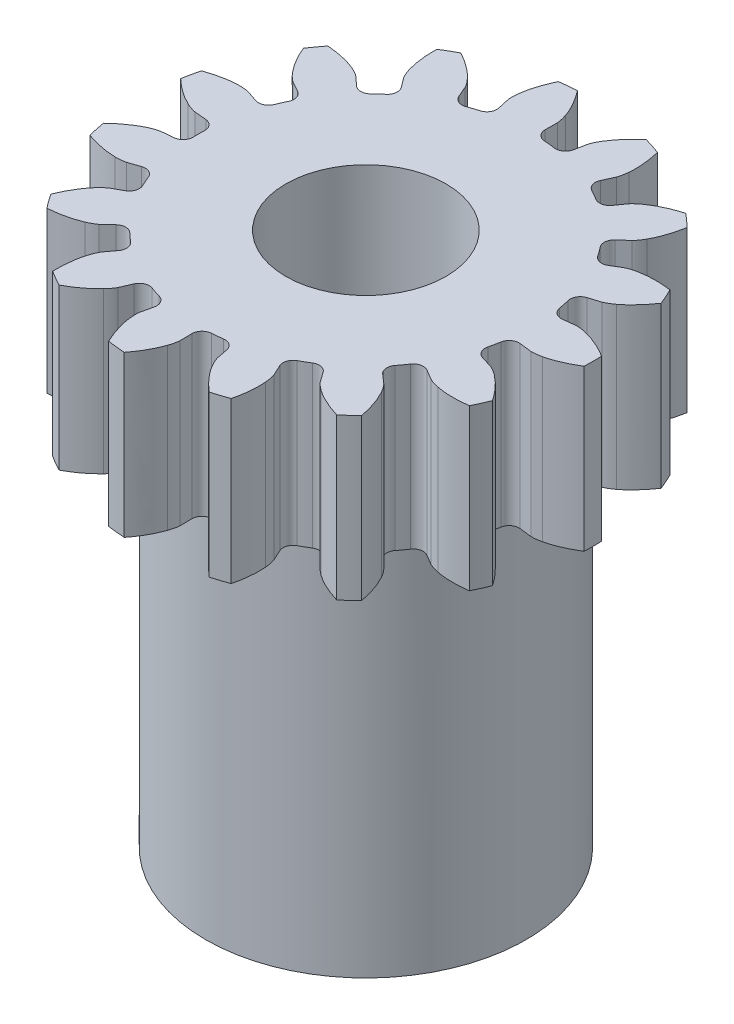
SolidWorks part; units mm, degrees
ref_plane "Front Plane" through (0, 0, 0) normal (0, 0, 1) x (1, 0, 0)
ref_plane "Top Plane" through (0, 0, 0) normal (0, 1, 0) x (1, 0, 0)
ref_plane "Right Plane" through (0, 0, 0) normal (1, 0, 0) x (0, 0, -1)
sketch "Sketch1" plane through (0, 0, 3) normal (0, -1, 0) x (1, 0, 0)
  line L0 (3.2832, -3.3946) -> (3.507, -3.4211)
  line L1 (3.507, -2.5789) -> (3.2832, -2.6054)
  line L2 (3.1599, -2.0251) -> (3.3751, -1.9583)
  line L3 (3.0325, -1.1889) -> (2.8389, -1.3041)
  line L4 (2.4902, -0.8241) -> (2.6596, -0.6756)
  line L5 (2.0336, -0.112) -> (1.9036, -0.296)
  line L6 (1.3899, 0.0006) -> (1.4842, 0.2052)
  line L7 (0.6832, 0.4655) -> (0.6393, 0.2445)
  line L8 (0.0493, 0.3065) -> (0.0523, 0.5318)
  line L9 (-0.7854, 0.4437) -> (-0.7357, 0.224)
  line L10 (-1.2998, 0.0407) -> (-1.3888, 0.2477)
  line L11 (-2.1182, -0.1735) -> (-1.9834, -0.354)
  line L12 (-2.4242, -0.7509) -> (-2.5897, -0.598)
  line L13 (-3.0847, -1.2794) -> (-2.8882, -1.3894)
  line L14 (-3.1294, -1.9314) -> (-3.3428, -1.8589)
  line L15 (-3.5179, -2.6828) -> (-3.2935, -2.7034)
  line L16 (-3.2935, -3.2966) -> (-3.5179, -3.3172)
  line L17 (-3.3428, -4.1411) -> (-3.1294, -4.0686)
  line L18 (-2.8882, -4.6106) -> (-3.0847, -4.7206)
  line L19 (-2.5897, -5.402) -> (-2.4242, -5.2491)
  line L20 (-1.9834, -5.646) -> (-2.1182, -5.8265)
  line L21 (-1.3888, -6.2477) -> (-1.2998, -6.0407)
  line L22 (-0.7357, -6.224) -> (-0.7854, -6.4437)
  line L23 (0.0523, -6.5318) -> (0.0493, -6.3065)
  line L24 (0.6393, -6.2445) -> (0.6832, -6.4655)
  line L25 (1.4842, -6.2052) -> (1.3899, -6.0006)
  line L26 (1.9036, -5.704) -> (2.0336, -5.888)
  line L27 (2.6596, -5.3244) -> (2.4902, -5.1759)
  line L28 (2.8389, -4.6959) -> (3.0325, -4.8111)
  line L29 (3.3751, -4.0417) -> (3.1599, -3.9749)
  arc A0 (3.0335, -3.7508) -> (3.0766, -3.548) centre (0, -3) ccw
  arc A1 (3.0766, -3.548) -> (3.2832, -3.3946) centre (3.2612, -3.5808) cw
  arc A2 (4.2475, -3.1638) -> (4.2475, -2.8362) centre (0.0006, -3) ccw
  arc A3 (3.2832, -2.6054) -> (3.0766, -2.452) centre (3.2612, -2.4192) cw
  arc A4 (3.0766, -2.452) -> (3.0335, -2.2492) centre (0, -3) ccw
  arc A5 (3.0335, -2.2492) -> (3.1599, -2.0251) centre (3.2155, -2.2042) cw
  arc A6 (3.9469, -1.4221) -> (3.8136, -1.1228) centre (0.0006, -2.9998) ccw
  arc A7 (2.8389, -1.3041) -> (2.5877, -1.2481) centre (2.743, -1.1429) cw
  arc A8 (2.5877, -1.2481) -> (2.4658, -1.0803) centre (0, -3) ccw
  arc A9 (2.4658, -1.0803) -> (2.4902, -0.8241) centre (2.6138, -0.9651) cw
  arc A10 (2.9638, 0.0469) -> (2.7204, 0.2661) centre (0.0004, -2.9995) ccw
  arc A11 (1.9036, -0.296) -> (1.6514, -0.347) centre (1.7505, -0.1878) cw
  arc A12 (1.6514, -0.347) -> (1.4719, -0.2433) centre (0, -3) ccw
  arc A13 (1.4719, -0.2433) -> (1.3899, 0.0006) centre (1.5602, -0.0779) cw
  arc A14 (1.4683, 0.9889) -> (1.1567, 1.0902) centre (0.0002, -2.9994) ccw
  arc A15 (0.6393, 0.2445) -> (0.4296, 0.0953) centre (0.4554, 0.2811) cw
  arc A16 (0.4296, 0.0953) -> (0.2234, 0.117) centre (0, -3) ccw
  arc A17 (0.2234, 0.117) -> (0.0493, 0.3065) centre (0.2368, 0.304) cw
  arc A18 (-0.2811, 1.2413) -> (-0.6069, 1.2071) centre (-0.0001, -2.9994) ccw
  arc A19 (-0.7357, 0.224) -> (-0.8665, 0.0025) centre (-0.9185, 0.1826) cw
  arc A20 (-0.8665, 0.0025) -> (-1.0637, -0.0616) centre (0, -3) ccw
  arc A21 (-1.0637, -0.0616) -> (-1.2998, 0.0407) centre (-1.1276, 0.1147) cw
  arc A22 (-1.9819, 0.7603) -> (-2.2656, 0.5965) centre (-0.0003, -2.9995) ccw
  arc A23 (-1.9834, -0.354) -> (-2.0128, -0.6096) centre (-2.1336, -0.4662) cw
  arc A24 (-2.0128, -0.6096) -> (-2.1669, -0.7483) centre (0, -3) ccw
  arc A25 (-2.1669, -0.7483) -> (-2.4242, -0.7509) centre (-2.2969, -0.6132) cw
  arc A26 (-3.34, -0.3709) -> (-3.5325, -0.6359) centre (-0.0005, -2.9996) ccw
  arc A27 (-2.8882, -1.3894) -> (-2.8111, -1.6349) centre (-2.9798, -1.553) cw
  arc A28 (-2.8111, -1.6349) -> (-2.8954, -1.8244) centre (0, -3) ccw
  arc A29 (-2.8954, -1.8244) -> (-3.1294, -1.9314) centre (-3.0692, -1.7538) cw
  arc A30 (-4.1206, -1.9567) -> (-4.1887, -2.2771) centre (-0.0006, -2.9999) ccw
  arc A31 (-3.2935, -2.7034) -> (-3.1233, -2.8963) centre (-3.3107, -2.8901) cw
  arc A32 (-3.1233, -2.8963) -> (-3.1233, -3.1037) centre (0, -3) ccw
  arc A33 (-3.1233, -3.1037) -> (-3.2935, -3.2966) centre (-3.3107, -3.1099) cw
  arc A34 (-4.1887, -3.7229) -> (-4.1206, -4.0433) centre (-0.0006, -3.0001) ccw
  arc A35 (-3.1294, -4.0686) -> (-2.8954, -4.1756) centre (-3.0692, -4.2462) cw
  arc A36 (-2.8954, -4.1756) -> (-2.8111, -4.3651) centre (0, -3) ccw
  arc A37 (-2.8111, -4.3651) -> (-2.8882, -4.6106) centre (-2.9798, -4.447) cw
  arc A38 (-3.5325, -5.3641) -> (-3.34, -5.6291) centre (-0.0005, -3.0004) ccw
  arc A39 (-2.4242, -5.2491) -> (-2.1669, -5.2517) centre (-2.2969, -5.3868) cw
  arc A40 (-2.1669, -5.2517) -> (-2.0128, -5.3904) centre (0, -3) ccw
  arc A41 (-2.0128, -5.3904) -> (-1.9834, -5.646) centre (-2.1336, -5.5338) cw
  arc A42 (-2.2656, -6.5965) -> (-1.9819, -6.7603) centre (-0.0003, -3.0005) ccw
  arc A43 (-1.2998, -6.0407) -> (-1.0637, -5.9384) centre (-1.1276, -6.1147) cw
  arc A44 (-1.0637, -5.9384) -> (-0.8665, -6.0025) centre (0, -3) ccw
  arc A45 (-0.8665, -6.0025) -> (-0.7357, -6.224) centre (-0.9185, -6.1826) cw
  arc A46 (-0.6069, -7.2071) -> (-0.2811, -7.2413) centre (-0.0001, -3.0006) ccw
  arc A47 (0.0493, -6.3065) -> (0.2234, -6.117) centre (0.2368, -6.304) cw
  arc A48 (0.2234, -6.117) -> (0.4296, -6.0953) centre (0, -3) ccw
  arc A49 (0.4296, -6.0953) -> (0.6393, -6.2445) centre (0.4554, -6.2811) cw
  arc A50 (1.1567, -7.0902) -> (1.4683, -6.9889) centre (0.0002, -3.0006) ccw
  arc A51 (1.3899, -6.0006) -> (1.4719, -5.7567) centre (1.5602, -5.9221) cw
  arc A52 (1.4719, -5.7567) -> (1.6514, -5.653) centre (0, -3) ccw
  arc A53 (1.6514, -5.653) -> (1.9036, -5.704) centre (1.7505, -5.8122) cw
  arc A54 (2.7204, -6.2661) -> (2.9638, -6.0469) centre (0.0004, -3.0005) ccw
  arc A55 (2.4902, -5.1759) -> (2.4658, -4.9197) centre (2.6138, -5.0349) cw
  arc A56 (2.4658, -4.9197) -> (2.5877, -4.7519) centre (0, -3) ccw
  arc A57 (2.5877, -4.7519) -> (2.8389, -4.6959) centre (2.743, -4.8571) cw
  arc A58 (3.8136, -4.8772) -> (3.9469, -4.5779) centre (0.0006, -3.0002) ccw
  arc A59 (3.1599, -3.9749) -> (3.0335, -3.7508) centre (3.2155, -3.7958) cw
  spline S0 degree 3 poles (3.507, -3.4211) (3.521, -3.4219) (3.535, -3.4216) (3.549, -3.4209) (3.5749, -3.4196) (3.6007, -3.4167) (3.6264, -3.4128) (3.6522, -3.4089) (3.6779, -3.404) (3.7033, -3.3983) knots 0 0 0 0 0.000042 0.000042 0.000042 0.00012 0.00012 0.00012 0.000198 0.000198 0.000198 0.000198
  spline S1 degree 3 poles (3.7033, -3.3983) (3.7685, -3.3834) (3.8326, -3.3634) (3.895, -3.3398) (3.9562, -3.3166) (4.0161, -3.29) (4.0746, -3.2606) (4.1336, -3.2309) (4.1912, -3.1985) (4.2475, -3.1638) knots 0 0 0 0 0.0002 0.0002 0.0002 0.000397 0.000397 0.000397 0.000594 0.000594 0.000594 0.000594
  spline S2 degree 3 poles (4.2475, -2.8362) (4.1907, -2.8012) (4.1324, -2.7684) (4.0728, -2.7385) (4.0144, -2.7092) (3.9545, -2.6826) (3.8934, -2.6596) (3.8314, -2.6363) (3.7679, -2.6164) (3.7033, -2.6017) knots 0 0 0 0 0.0002 0.0002 0.0002 0.000396 0.000396 0.000396 0.000595 0.000595 0.000595 0.000595
  spline S3 degree 3 poles (3.7033, -2.6017) (3.676, -2.5956) (3.6484, -2.5904) (3.6207, -2.5864) (3.6019, -2.5837) (3.5831, -2.5815) (3.5642, -2.5801) (3.5452, -2.5787) (3.526, -2.5779) (3.507, -2.5789) knots 0 0 0 0 0.000084 0.000084 0.000084 0.000141 0.000141 0.000141 0.000198 0.000198 0.000198 0.000198
  spline S4 degree 3 poles (3.3751, -1.9583) (3.3882, -1.9533) (3.4009, -1.9473) (3.4134, -1.941) (3.4365, -1.9292) (3.4589, -1.9161) (3.4807, -1.9021) (3.5027, -1.8881) (3.5242, -1.8731) (3.5452, -1.8575) knots 0 0 0 0 0.000042 0.000042 0.000042 0.00012 0.00012 0.00012 0.000198 0.000198 0.000198 0.000198
  spline S5 degree 3 poles (3.5452, -1.8575) (3.5986, -1.8175) (3.649, -1.7731) (3.6965, -1.7261) (3.743, -1.6801) (3.7869, -1.6314) (3.8283, -1.5808) (3.8702, -1.5297) (3.9096, -1.4766) (3.9469, -1.4221) knots 0 0 0 0 0.0002 0.0002 0.0002 0.000397 0.000397 0.000397 0.000594 0.000594 0.000594 0.000594
  spline S6 degree 3 poles (3.8136, -1.1228) (3.7475, -1.1139) (3.681, -1.1076) (3.6144, -1.1046) (3.5491, -1.1016) (3.4835, -1.1016) (3.4183, -1.1055) (3.3522, -1.1093) (3.2861, -1.1171) (3.2212, -1.1299) knots 0 0 0 0 0.0002 0.0002 0.0002 0.000396 0.000396 0.000396 0.000595 0.000595 0.000595 0.000595
  spline S7 degree 3 poles (3.2212, -1.1299) (3.1937, -1.1354) (3.1664, -1.1419) (3.1394, -1.1495) (3.1212, -1.1546) (3.1031, -1.1603) (3.0853, -1.1667) (3.0673, -1.1731) (3.0495, -1.1802) (3.0325, -1.1889) knots 0 0 0 0 0.000084 0.000084 0.000084 0.000141 0.000141 0.000141 0.000198 0.000198 0.000198 0.000198
  spline S8 degree 3 poles (2.6596, -0.6756) (2.6695, -0.6657) (2.6787, -0.655) (2.6875, -0.6442) (2.7039, -0.6241) (2.719, -0.6029) (2.7333, -0.5813) (2.7476, -0.5595) (2.7612, -0.5371) (2.774, -0.5144) knots 0 0 0 0 0.000042 0.000042 0.000042 0.00012 0.00012 0.00012 0.000198 0.000198 0.000198 0.000198
  spline S9 degree 3 poles (2.774, -0.5144) (2.8066, -0.456) (2.8345, -0.395) (2.8588, -0.3328) (2.8825, -0.2718) (2.9028, -0.2095) (2.9201, -0.1464) (2.9375, -0.0827) (2.952, -0.0181) (2.9638, 0.0469) knots 0 0 0 0 0.0002 0.0002 0.0002 0.000397 0.000397 0.000397 0.000594 0.000594 0.000594 0.000594
  spline S10 degree 3 poles (2.7204, 0.2661) (2.6564, 0.2473) (2.593, 0.226) (2.5309, 0.2017) (2.4701, 0.1778) (2.4102, 0.1511) (2.3522, 0.1211) (2.2934, 0.0907) (2.2362, 0.0568) (2.1821, 0.0186) knots 0 0 0 0 0.0002 0.0002 0.0002 0.000396 0.000396 0.000396 0.000595 0.000595 0.000595 0.000595
  spline S11 degree 3 poles (2.1821, 0.0186) (2.1592, 0.0024) (2.1369, -0.0146) (2.1153, -0.0325) (2.1008, -0.0447) (2.0865, -0.0572) (2.0728, -0.0703) (2.0591, -0.0835) (2.0457, -0.0972) (2.0336, -0.112) knots 0 0 0 0 0.000084 0.000084 0.000084 0.000141 0.000141 0.000141 0.000198 0.000198 0.000198 0.000198
  spline S12 degree 3 poles (1.4842, 0.2052) (1.4893, 0.2183) (1.4933, 0.2317) (1.497, 0.2453) (1.5037, 0.2703) (1.509, 0.2957) (1.5132, 0.3213) (1.5175, 0.3471) (1.5207, 0.373) (1.5232, 0.399) knots 0 0 0 0 0.000042 0.000042 0.000042 0.00012 0.00012 0.00012 0.000198 0.000198 0.000198 0.000198
  spline S13 degree 3 poles (1.5232, 0.399) (1.5292, 0.4656) (1.5299, 0.5327) (1.5268, 0.5994) (1.5237, 0.6647) (1.5168, 0.73) (1.507, 0.7946) (1.497, 0.8599) (1.4839, 0.9248) (1.4683, 0.9889) knots 0 0 0 0 0.0002 0.0002 0.0002 0.000397 0.000397 0.000397 0.000594 0.000594 0.000594 0.000594
  spline S14 degree 3 poles (1.1567, 1.0902) (1.1059, 1.047) (1.0567, 1.0018) (1.0099, 0.9543) (0.964, 0.9078) (0.9202, 0.859) (0.8794, 0.808) (0.838, 0.7563) (0.7996, 0.702) (0.7656, 0.6452) knots 0 0 0 0 0.0002 0.0002 0.0002 0.000396 0.000396 0.000396 0.000595 0.000595 0.000595 0.000595
  spline S15 degree 3 poles (0.7656, 0.6452) (0.7514, 0.621) (0.7379, 0.5964) (0.7255, 0.5713) (0.7171, 0.5543) (0.7092, 0.537) (0.702, 0.5195) (0.6948, 0.5018) (0.6881, 0.4839) (0.6832, 0.4655) knots 0 0 0 0 0.000084 0.000084 0.000084 0.000141 0.000141 0.000141 0.000198 0.000198 0.000198 0.000198
  spline S16 degree 3 poles (0.0523, 0.5318) (0.0515, 0.5458) (0.0497, 0.5597) (0.0476, 0.5736) (0.0436, 0.5992) (0.038, 0.6246) (0.0315, 0.6496) (0.0249, 0.6749) (0.0173, 0.6999) (0.009, 0.7247) knots 0 0 0 0 0.000042 0.000042 0.000042 0.00012 0.00012 0.00012 0.000198 0.000198 0.000198 0.000198
  spline S17 degree 3 poles (0.009, 0.7247) (-0.0126, 0.7879) (-0.0392, 0.8495) (-0.0692, 0.9092) (-0.0986, 0.9677) (-0.1314, 1.0245) (-0.1667, 1.0795) (-0.2024, 1.1351) (-0.2407, 1.189) (-0.2811, 1.2413) knots 0 0 0 0 0.0002 0.0002 0.0002 0.000397 0.000397 0.000397 0.000594 0.000594 0.000594 0.000594
  spline S18 degree 3 poles (-0.6069, 1.2071) (-0.6358, 1.1469) (-0.6623, 1.0856) (-0.6858, 1.0232) (-0.7088, 0.962) (-0.729, 0.8997) (-0.7455, 0.8365) (-0.7622, 0.7724) (-0.7753, 0.7072) (-0.7832, 0.6414) knots 0 0 0 0 0.0002 0.0002 0.0002 0.000396 0.000396 0.000396 0.000595 0.000595 0.000595 0.000595
  spline S19 degree 3 poles (-0.7832, 0.6414) (-0.7864, 0.6136) (-0.7887, 0.5856) (-0.7898, 0.5576) (-0.7906, 0.5387) (-0.7908, 0.5197) (-0.7902, 0.5008) (-0.7896, 0.4817) (-0.7884, 0.4626) (-0.7854, 0.4437) knots 0 0 0 0 0.000084 0.000084 0.000084 0.000141 0.000141 0.000141 0.000198 0.000198 0.000198 0.000198
  spline S20 degree 3 poles (-1.3888, 0.2477) (-1.3951, 0.2602) (-1.4024, 0.2722) (-1.41, 0.284) (-1.4241, 0.3058) (-1.4395, 0.3267) (-1.4557, 0.3469) (-1.472, 0.3673) (-1.4891, 0.3871) (-1.5068, 0.4063) knots 0 0 0 0 0.000042 0.000042 0.000042 0.00012 0.00012 0.00012 0.000198 0.000198 0.000198 0.000198
  spline S21 degree 3 poles (-1.5068, 0.4063) (-1.5522, 0.4553) (-1.6016, 0.5008) (-1.6533, 0.5431) (-1.7039, 0.5845) (-1.757, 0.6231) (-1.8116, 0.659) (-1.8668, 0.6953) (-1.9237, 0.729) (-1.9819, 0.7603) knots 0 0 0 0 0.0002 0.0002 0.0002 0.000397 0.000397 0.000397 0.000594 0.000594 0.000594 0.000594
  spline S22 degree 3 poles (-2.2656, 0.5965) (-2.2675, 0.5298) (-2.2668, 0.463) (-2.2629, 0.3964) (-2.259, 0.3312) (-2.2521, 0.266) (-2.2415, 0.2016) (-2.2307, 0.1362) (-2.2161, 0.0713) (-2.1966, 0.0081) knots 0 0 0 0 0.0002 0.0002 0.0002 0.000396 0.000396 0.000396 0.000595 0.000595 0.000595 0.000595
  spline S23 degree 3 poles (-2.1966, 0.0081) (-2.1882, -0.0187) (-2.1789, -0.0452) (-2.1686, -0.0712) (-2.1615, -0.0888) (-2.154, -0.1062) (-2.1458, -0.1233) (-2.1375, -0.1405) (-2.1286, -0.1574) (-2.1182, -0.1735) knots 0 0 0 0 0.000084 0.000084 0.000084 0.000141 0.000141 0.000141 0.000198 0.000198 0.000198 0.000198
  spline S24 degree 3 poles (-2.5897, -0.598) (-2.6006, -0.5891) (-2.6121, -0.5811) (-2.6239, -0.5734) (-2.6456, -0.5593) (-2.6682, -0.5465) (-2.6912, -0.5345) (-2.7143, -0.5225) (-2.738, -0.5114) (-2.762, -0.501) knots 0 0 0 0 0.000042 0.000042 0.000042 0.00012 0.00012 0.00012 0.000198 0.000198 0.000198 0.000198
  spline S25 degree 3 poles (-2.762, -0.501) (-2.8234, -0.4747) (-2.887, -0.4533) (-2.9515, -0.4357) (-3.0145, -0.4184) (-3.0787, -0.4048) (-3.1432, -0.3942) (-3.2084, -0.3835) (-3.2741, -0.3759) (-3.34, -0.3709) knots 0 0 0 0 0.0002 0.0002 0.0002 0.000397 0.000397 0.000397 0.000594 0.000594 0.000594 0.000594
  spline S26 degree 3 poles (-3.5325, -0.6359) (-3.5072, -0.6976) (-3.4793, -0.7584) (-3.4487, -0.8176) (-3.4186, -0.8756) (-3.3858, -0.9323) (-3.3499, -0.9869) (-3.3135, -1.0422) (-3.2737, -1.0956) (-3.2302, -1.1454) knots 0 0 0 0 0.0002 0.0002 0.0002 0.000396 0.000396 0.000396 0.000595 0.000595 0.000595 0.000595
  spline S27 degree 3 poles (-3.2302, -1.1454) (-3.2116, -1.1664) (-3.1924, -1.1869) (-3.1723, -1.2064) (-3.1587, -1.2197) (-3.1448, -1.2325) (-3.1303, -1.2447) (-3.1158, -1.2571) (-3.1007, -1.269) (-3.0847, -1.2794) knots 0 0 0 0 0.000084 0.000084 0.000084 0.000141 0.000141 0.000141 0.000198 0.000198 0.000198 0.000198
  spline S28 degree 3 poles (-3.3428, -1.8589) (-3.3563, -1.8553) (-3.3701, -1.8527) (-3.384, -1.8504) (-3.4096, -1.8463) (-3.4354, -1.8438) (-3.4613, -1.8423) (-3.4874, -1.8407) (-3.5135, -1.8402) (-3.5396, -1.8405) knots 0 0 0 0 0.000042 0.000042 0.000042 0.00012 0.00012 0.00012 0.000198 0.000198 0.000198 0.000198
  spline S29 degree 3 poles (-3.5396, -1.8405) (-3.6064, -1.8414) (-3.6733, -1.8477) (-3.7393, -1.8578) (-3.8039, -1.8677) (-3.8681, -1.8814) (-3.9314, -1.8979) (-3.9952, -1.9147) (-4.0584, -1.9345) (-4.1206, -1.9567) knots 0 0 0 0 0.0002 0.0002 0.0002 0.000397 0.000397 0.000397 0.000594 0.000594 0.000594 0.000594
  spline S30 degree 3 poles (-4.1887, -2.2771) (-4.1404, -2.3232) (-4.0903, -2.3673) (-4.0382, -2.409) (-3.9871, -2.4498) (-3.9341, -2.4882) (-3.8791, -2.5235) (-3.8233, -2.5592) (-3.7653, -2.5918) (-3.7052, -2.6196) knots 0 0 0 0 0.0002 0.0002 0.0002 0.000396 0.000396 0.000396 0.000595 0.000595 0.000595 0.000595
  spline S31 degree 3 poles (-3.7052, -2.6196) (-3.6797, -2.6313) (-3.6539, -2.6421) (-3.6276, -2.6518) (-3.6098, -2.6584) (-3.5918, -2.6644) (-3.5736, -2.6697) (-3.5553, -2.675) (-3.5367, -2.6798) (-3.5179, -2.6828) knots 0 0 0 0 0.000084 0.000084 0.000084 0.000141 0.000141 0.000141 0.000198 0.000198 0.000198 0.000198
  spline S32 degree 3 poles (-3.5179, -3.3172) (-3.5317, -3.3194) (-3.5454, -3.3226) (-3.559, -3.3262) (-3.584, -3.3329) (-3.6087, -3.3411) (-3.6329, -3.3502) (-3.6574, -3.3594) (-3.6815, -3.3695) (-3.7052, -3.3804) knots 0 0 0 0 0.000042 0.000042 0.000042 0.00012 0.00012 0.00012 0.000198 0.000198 0.000198 0.000198
  spline S33 degree 3 poles (-3.7052, -3.3804) (-3.7659, -3.4085) (-3.8244, -3.4414) (-3.8806, -3.4775) (-3.9356, -3.5128) (-3.9887, -3.5514) (-4.0397, -3.5922) (-4.0913, -3.6335) (-4.1409, -3.6773) (-4.1887, -3.7229) knots 0 0 0 0 0.0002 0.0002 0.0002 0.000397 0.000397 0.000397 0.000594 0.000594 0.000594 0.000594
  spline S34 degree 3 poles (-4.1206, -4.0433) (-4.0578, -4.0658) (-3.994, -4.0857) (-3.9295, -4.1026) (-3.8662, -4.1191) (-3.8021, -4.1326) (-3.7375, -4.1424) (-3.6721, -4.1524) (-3.6058, -4.1586) (-3.5396, -4.1595) knots 0 0 0 0 0.0002 0.0002 0.0002 0.000396 0.000396 0.000396 0.000595 0.000595 0.000595 0.000595
  spline S35 degree 3 poles (-3.5396, -4.1595) (-3.5116, -4.1598) (-3.4835, -4.1592) (-3.4556, -4.1574) (-3.4367, -4.1561) (-3.4178, -4.1543) (-3.399, -4.1518) (-3.3801, -4.1492) (-3.3612, -4.146) (-3.3428, -4.1411) knots 0 0 0 0 0.000084 0.000084 0.000084 0.000141 0.000141 0.000141 0.000198 0.000198 0.000198 0.000198
  spline S36 degree 3 poles (-3.0847, -4.7206) (-3.0965, -4.7283) (-3.1077, -4.7368) (-3.1186, -4.7456) (-3.1388, -4.7618) (-3.158, -4.7794) (-3.1764, -4.7976) (-3.195, -4.8159) (-3.2129, -4.835) (-3.2302, -4.8546) knots 0 0 0 0 0.000042 0.000042 0.000042 0.00012 0.00012 0.00012 0.000198 0.000198 0.000198 0.000198
  spline S37 degree 3 poles (-3.2302, -4.8546) (-3.2741, -4.9049) (-3.3142, -4.9587) (-3.3509, -5.0146) (-3.3868, -5.0692) (-3.4196, -5.126) (-3.4496, -5.1841) (-3.4799, -5.2428) (-3.5074, -5.303) (-3.5325, -5.3641) knots 0 0 0 0 0.0002 0.0002 0.0002 0.000397 0.000397 0.000397 0.000594 0.000594 0.000594 0.000594
  spline S38 degree 3 poles (-3.34, -5.6291) (-3.2735, -5.6241) (-3.2071, -5.6164) (-3.1413, -5.6055) (-3.0768, -5.5948) (-3.0127, -5.5812) (-2.9497, -5.5639) (-2.8859, -5.5463) (-2.8228, -5.525) (-2.762, -5.499) knots 0 0 0 0 0.0002 0.0002 0.0002 0.000396 0.000396 0.000396 0.000595 0.000595 0.000595 0.000595
  spline S39 degree 3 poles (-2.762, -5.499) (-2.7363, -5.4878) (-2.7109, -5.4759) (-2.6861, -5.4628) (-2.6693, -5.454) (-2.6528, -5.4447) (-2.6367, -5.4347) (-2.6204, -5.4247) (-2.6045, -5.414) (-2.5897, -5.402) knots 0 0 0 0 0.000084 0.000084 0.000084 0.000141 0.000141 0.000141 0.000198 0.000198 0.000198 0.000198
  spline S40 degree 3 poles (-2.1182, -5.8265) (-2.1258, -5.8383) (-2.1326, -5.8506) (-2.139, -5.8631) (-2.1508, -5.8862) (-2.1612, -5.91) (-2.1707, -5.9341) (-2.1802, -5.9584) (-2.1888, -5.9831) (-2.1966, -6.0081) knots 0 0 0 0 0.000042 0.000042 0.000042 0.00012 0.00012 0.00012 0.000198 0.000198 0.000198 0.000198
  spline S41 degree 3 poles (-2.1966, -6.0081) (-2.2163, -6.0719) (-2.231, -6.1374) (-2.2418, -6.2033) (-2.2523, -6.2679) (-2.2592, -6.3331) (-2.263, -6.3984) (-2.2668, -6.4643) (-2.2675, -6.5305) (-2.2656, -6.5965) knots 0 0 0 0 0.0002 0.0002 0.0002 0.000397 0.000397 0.000397 0.000594 0.000594 0.000594 0.000594
  spline S42 degree 3 poles (-1.9819, -6.7603) (-1.9232, -6.7286) (-1.8657, -6.6946) (-1.81, -6.6579) (-1.7554, -6.622) (-1.7024, -6.5834) (-1.6519, -6.542) (-1.6007, -6.5) (-1.5518, -6.4549) (-1.5068, -6.4063) knots 0 0 0 0 0.0002 0.0002 0.0002 0.000396 0.000396 0.000396 0.000595 0.000595 0.000595 0.000595
  spline S43 degree 3 poles (-1.5068, -6.4063) (-1.4878, -6.3857) (-1.4695, -6.3644) (-1.4521, -6.3424) (-1.4404, -6.3275) (-1.4291, -6.3123) (-1.4184, -6.2966) (-1.4077, -6.2809) (-1.3974, -6.2647) (-1.3888, -6.2477) knots 0 0 0 0 0.000084 0.000084 0.000084 0.000141 0.000141 0.000141 0.000198 0.000198 0.000198 0.000198
  spline S44 degree 3 poles (-0.7854, -6.4437) (-0.7876, -6.4576) (-0.7888, -6.4716) (-0.7895, -6.4856) (-0.791, -6.5115) (-0.7908, -6.5375) (-0.7896, -6.5633) (-0.7884, -6.5894) (-0.7862, -6.6155) (-0.7832, -6.6414) knots 0 0 0 0 0.000042 0.000042 0.000042 0.00012 0.00012 0.00012 0.000198 0.000198 0.000198 0.000198
  spline S45 degree 3 poles (-0.7832, -6.6414) (-0.7752, -6.7078) (-0.762, -6.7736) (-0.745, -6.8382) (-0.7284, -6.9015) (-0.7082, -6.9638) (-0.6851, -7.025) (-0.6618, -7.0868) (-0.6355, -7.1475) (-0.6069, -7.2071) knots 0 0 0 0 0.0002 0.0002 0.0002 0.000397 0.000397 0.000397 0.000594 0.000594 0.000594 0.000594
  spline S46 degree 3 poles (-0.2811, -7.2413) (-0.2403, -7.1885) (-0.2016, -7.134) (-0.1657, -7.0778) (-0.1304, -7.0228) (-0.0977, -6.966) (-0.0684, -6.9076) (-0.0387, -6.8484) (-0.0124, -6.7874) (0.009, -6.7247) knots 0 0 0 0 0.0002 0.0002 0.0002 0.000396 0.000396 0.000396 0.000595 0.000595 0.000595 0.000595
  spline S47 degree 3 poles (0.009, -6.7247) (0.0179, -6.6981) (0.026, -6.6712) (0.0329, -6.6441) (0.0376, -6.6257) (0.0417, -6.6072) (0.0451, -6.5886) (0.0485, -6.5698) (0.0512, -6.5508) (0.0523, -6.5318) knots 0 0 0 0 0.000084 0.000084 0.000084 0.000141 0.000141 0.000141 0.000198 0.000198 0.000198 0.000198
  spline S48 degree 3 poles (0.6832, -6.4655) (0.6868, -6.479) (0.6914, -6.4923) (0.6964, -6.5054) (0.7057, -6.5296) (0.7164, -6.5533) (0.728, -6.5764) (0.7397, -6.5998) (0.7523, -6.6227) (0.7656, -6.6452) knots 0 0 0 0 0.000042 0.000042 0.000042 0.00012 0.00012 0.00012 0.000198 0.000198 0.000198 0.000198
  spline S49 degree 3 poles (0.7656, -6.6452) (0.7999, -6.7025) (0.8387, -6.7573) (0.8805, -6.8094) (0.9214, -6.8604) (0.9653, -6.9092) (1.0113, -6.9557) (1.0577, -7.0026) (1.1064, -7.0474) (1.1567, -7.0902) knots 0 0 0 0 0.0002 0.0002 0.0002 0.000397 0.000397 0.000397 0.000594 0.000594 0.000594 0.000594
  spline S50 degree 3 poles (1.4683, -6.9889) (1.4841, -6.9241) (1.4973, -6.8586) (1.5073, -6.7927) (1.5171, -6.7281) (1.5238, -6.6629) (1.5269, -6.5976) (1.5299, -6.5315) (1.5291, -6.465) (1.5232, -6.399) knots 0 0 0 0 0.0002 0.0002 0.0002 0.000396 0.000396 0.000396 0.000595 0.000595 0.000595 0.000595
  spline S51 degree 3 poles (1.5232, -6.399) (1.5205, -6.3711) (1.517, -6.3433) (1.5122, -6.3157) (1.509, -6.297) (1.5053, -6.2784) (1.5008, -6.26) (1.4962, -6.2415) (1.4911, -6.223) (1.4842, -6.2052) knots 0 0 0 0 0.000084 0.000084 0.000084 0.000141 0.000141 0.000141 0.000198 0.000198 0.000198 0.000198
  spline S52 degree 3 poles (2.0336, -5.888) (2.0425, -5.8989) (2.0521, -5.9091) (2.062, -5.9191) (2.0803, -5.9374) (2.0997, -5.9547) (2.1197, -5.9711) (2.1399, -5.9877) (2.1608, -6.0035) (2.1821, -6.0186) knots 0 0 0 0 0.000042 0.000042 0.000042 0.00012 0.00012 0.00012 0.000198 0.000198 0.000198 0.000198
  spline S53 degree 3 poles (2.1821, -6.0186) (2.2367, -6.0571) (2.2944, -6.0913) (2.3538, -6.1219) (2.4119, -6.1519) (2.4718, -6.1786) (2.5328, -6.2024) (2.5943, -6.2264) (2.657, -6.2475) (2.7204, -6.2661) knots 0 0 0 0 0.0002 0.0002 0.0002 0.000397 0.000397 0.000397 0.000594 0.000594 0.000594 0.000594
  spline S54 degree 3 poles (2.9638, -6.0469) (2.9519, -5.9812) (2.9373, -5.916) (2.9196, -5.8517) (2.9022, -5.7887) (2.8819, -5.7264) (2.8581, -5.6656) (2.834, -5.6039) (2.8063, -5.5434) (2.774, -5.4856) knots 0 0 0 0 0.0002 0.0002 0.0002 0.000396 0.000396 0.000396 0.000595 0.000595 0.000595 0.000595
  spline S55 degree 3 poles (2.774, -5.4856) (2.7602, -5.4612) (2.7457, -5.4372) (2.7301, -5.4139) (2.7196, -5.3982) (2.7086, -5.3827) (2.697, -5.3677) (2.6853, -5.3526) (2.6731, -5.3379) (2.6596, -5.3244) knots 0 0 0 0 0.000084 0.000084 0.000084 0.000141 0.000141 0.000141 0.000198 0.000198 0.000198 0.000198
  spline S56 degree 3 poles (3.0325, -4.8111) (3.045, -4.8175) (3.0579, -4.823) (3.071, -4.828) (3.0952, -4.8373) (3.12, -4.8452) (3.1449, -4.8521) (3.1701, -4.859) (3.1956, -4.865) (3.2212, -4.8701) knots 0 0 0 0 0.000042 0.000042 0.000042 0.00012 0.00012 0.00012 0.000198 0.000198 0.000198 0.000198
  spline S57 degree 3 poles (3.2212, -4.8701) (3.2867, -4.8831) (3.3534, -4.8908) (3.4201, -4.8947) (3.4854, -4.8984) (3.551, -4.8984) (3.6163, -4.8954) (3.6823, -4.8923) (3.7482, -4.886) (3.8136, -4.8772) knots 0 0 0 0 0.0002 0.0002 0.0002 0.000397 0.000397 0.000397 0.000594 0.000594 0.000594 0.000594
  spline S58 degree 3 poles (3.9469, -4.5779) (3.9092, -4.5229) (3.8694, -4.4692) (3.8271, -4.4177) (3.7856, -4.3672) (3.7417, -4.3185) (3.6952, -4.2726) (3.6481, -4.2261) (3.5982, -4.1821) (3.5452, -4.1425) knots 0 0 0 0 0.0002 0.0002 0.0002 0.000396 0.000396 0.000396 0.000595 0.000595 0.000595 0.000595
  spline S59 degree 3 poles (3.5452, -4.1425) (3.5227, -4.1257) (3.4996, -4.1098) (3.4759, -4.0948) (3.4599, -4.0847) (3.4435, -4.075) (3.4268, -4.0661) (3.41, -4.057) (3.3929, -4.0485) (3.3751, -4.0417) knots 0 0 0 0 0.000084 0.000084 0.000084 0.000141 0.000141 0.000141 0.000198 0.000198 0.000198 0.000198
extrude "Gear" add sketch "Sketch1" against normal blind 1.5 and the other way blind 1.5
sketch "Sketch2" plane through (0, -1.5, 0) normal (0, -1, 0) x (-1, 0, 0)
  circle A0 centre (0, 0) radius 3
  dimension "D1" = 6
extrude "Boss-Extrude2" add sketch "Sketch2" along normal blind 7
sketch "Sketch3" plane through (0, -8.5, 0) normal (0, -1, 0) x (1, 0, 0)
  circle A0 centre (0, 0) radius 1.5
  dimension "D1" = 3
extrude "Cut-Extrude1" cut sketch "Sketch3" against normal up to next
